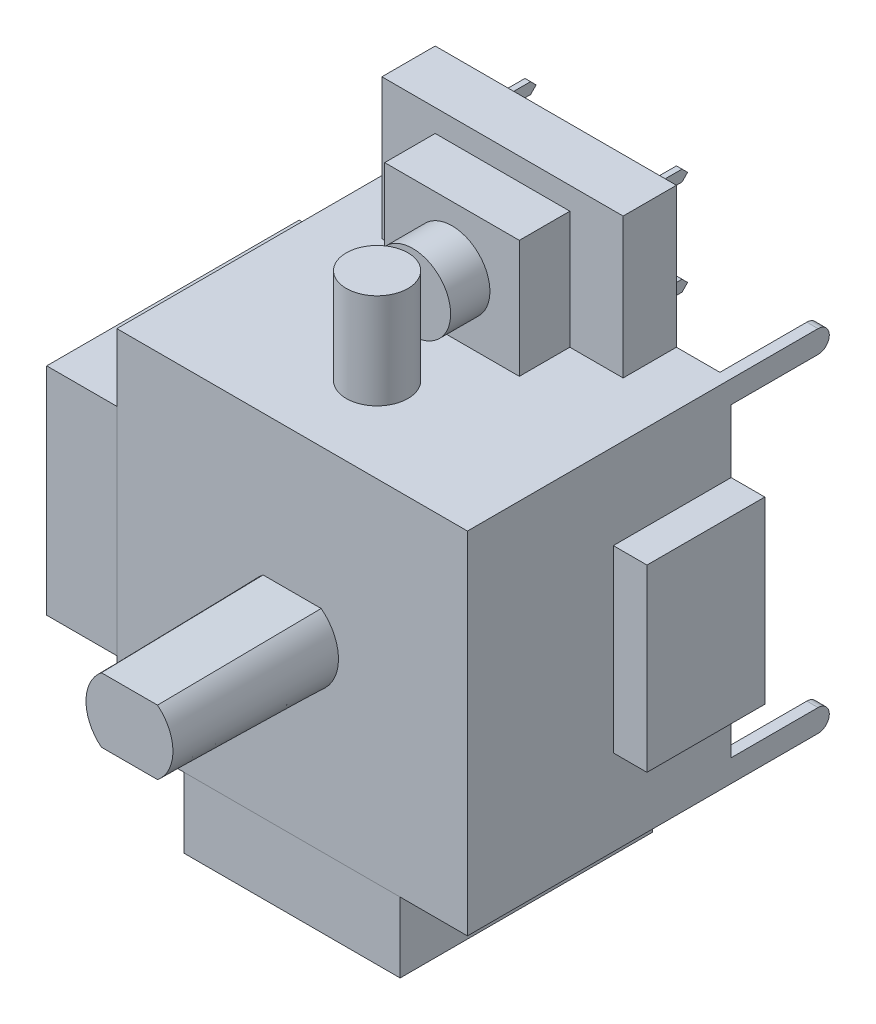
SolidWorks part; units mm, degrees
ref_plane "Front Plane" through (0, 0, 0) normal (0, 0, 1) x (1, 0, 0)
ref_plane "Top Plane" through (0, 0, 0) normal (0, 1, 0) x (1, 0, 0)
ref_plane "Right Plane" through (0, 0, 0) normal (1, 0, 0) x (0, 0, -1)
sketch "Sketch1" plane through (0, 0, 0) normal (0, 0, 1) x (1, 0, 0)
  line L1 (0, 0) -> (15.875, 0)
  line L2 (0, 0) -> (0, 15.875)
  line L3 (0, 15.875) -> (15.875, 15.875)
  line L4 (15.875, 0) -> (15.875, 15.875)
  dimension "D1" = 15.875
extrude "Boss-Extrude1" add sketch "Sketch1" along normal blind 11.938
sketch "Sketch2" plane through (0, 0, 0) normal (0, 0, -1) x (-1, 0, 0)
  line L0 (-7.9375, 15.875) -> (-7.9375, 24.013) construction
  line L1 (-15.875, 15.875) -> (0, 15.875) construction
  line L3 (-13.3985, 15.875) -> (-2.4765, 15.875)
  line L4 (-13.3985, 15.875) -> (-13.3985, 22.225)
  line L5 (-13.3985, 22.225) -> (-2.4765, 22.225)
  line L6 (-2.4765, 15.875) -> (-2.4765, 22.225)
  point P8 (-7.9375, 22.225)
  dimension "D1" = 10.922
  dimension "D2" = 6.35
extrude "Boss-Extrude2" add sketch "Sketch2" against normal blind 2.413
sketch "Sketch3" plane through (15.875, 0, 0) normal (1, 0, 0) x (0, 0, -1)
  line L0 (0, 0) -> (0, 15.875) construction
  line L1 (0, 3.8735) -> (-5.334, 3.8735)
  line L2 (0, 3.8735) -> (0, 12.0015)
  line L3 (0, 12.0015) -> (-5.334, 12.0015)
  line L4 (-5.334, 3.8735) -> (-5.334, 12.0015)
  line L5 (-11.938, 7.9375) -> (0, 7.9375) construction
  line L6 (-11.938, 0) -> (-11.938, 15.875) construction
  point P10 (-5.334, 7.9375)
  dimension "D1" = 8.128
  dimension "D2" = 5.334
extrude "Boss-Extrude3" add sketch "Sketch3" along normal blind 1.524
sketch "Sketch4" plane through (0, 0, 2.413) normal (0, 0, 1) x (1, 0, 0)
  line L0 (7.9375, 22.225) -> (7.9375, 15.875) construction
  line L1 (2.4765, 22.225) -> (13.3985, 22.225) construction
  line L2 (13.3985, 15.875) -> (2.4765, 15.875) construction
  line L3 (15.875, 15.875) -> (0, 15.875) construction
  line L4 (4.8895, 15.875) -> (10.9855, 15.875)
  line L5 (4.8895, 15.875) -> (4.8895, 21.209)
  line L6 (4.8895, 21.209) -> (10.9855, 21.209)
  line L7 (10.9855, 15.875) -> (10.9855, 21.209)
  point P12 (7.9375, 21.209)
  dimension "D1" = 6.096
  dimension "D2" = 5.334
extrude "Boss-Extrude4" add sketch "Sketch4" along normal blind 2.286
sketch "Sketch5" plane through (0, 0, 4.699) normal (0, 0, 1) x (1, 0, 0)
  line L0 (7.9375, 21.209) -> (7.9375, 15.875) construction
  line L1 (10.9855, 21.209) -> (4.8895, 21.209) construction
  line L2 (4.8895, 15.875) -> (10.9855, 15.875) construction
  line L3 (4.8895, 18.542) -> (10.9855, 18.542) construction
  line L4 (4.8895, 21.209) -> (4.8895, 15.875) construction
  line L5 (10.9855, 15.875) -> (10.9855, 21.209) construction
  circle A0 centre (7.9375, 18.542) radius 1.7145
  dimension "D1" = 3.429
extrude "Boss-Extrude5" add sketch "Sketch5" along normal blind 1.778
sketch "Sketch6" plane through (0, 15.875, 0) normal (0, 1, 0) x (1, 0, 0)
  line L0 (7.9375, -11.938) -> (7.9375, -4.699) construction
  line L1 (15.875, -11.938) -> (0, -11.938) construction
  line L2 (10.9855, -4.699) -> (4.8895, -4.699) construction
  circle A0 centre (7.9375, -8.0902) radius 1.397
  dimension "D1" = 2.794
extrude "Boss-Extrude6" add sketch "Sketch6" along normal blind 4.318
sketch "Sketch7" plane through (0, 0, 0) normal (0, -1, 0) x (1, 0, 0)
  line L0 (7.9375, 11.938) -> (7.9375, 0) construction
  line L1 (0, 11.938) -> (15.875, 11.938) construction
  line L2 (0, 0) -> (15.875, 0) construction
  line L4 (3.048, 11.938) -> (12.827, 11.938)
  line L5 (3.048, 11.938) -> (3.048, 0.508)
  line L6 (3.048, 0.508) -> (12.827, 0.508)
  line L7 (12.827, 11.938) -> (12.827, 0.508)
  point P10 (7.9375, 0.508)
  dimension "D1" = 9.779
  dimension "D2" = 11.43
extrude "Boss-Extrude7" add sketch "Sketch7" along normal blind 3.175 separate body
sketch "Sketch8" plane through (0, 0, 0) normal (-1, 0, 0) x (0, 0, 1)
  line L0 (11.938, 7.9375) -> (0, 7.9375) construction
  line L1 (11.938, 15.875) -> (11.938, 0) construction
  line L2 (0, 15.875) -> (0, 0) construction
  line L4 (11.938, 12.827) -> (0.508, 12.827)
  line L5 (11.938, 12.827) -> (11.938, 3.048)
  line L6 (11.938, 3.048) -> (0.508, 3.048)
  line L7 (0.508, 12.827) -> (0.508, 3.048)
  point P10 (0.508, 7.9375)
  dimension "D1" = 9.779
  dimension "D2" = 11.43
extrude "Boss-Extrude8" add sketch "Sketch8" along normal blind 3.175 separate body
sketch "Sketch9" plane through (-3.175, 0, 0) normal (-1, 0, 0) x (0, 0, 1)
  line L0 (11.938, 7.9375) -> (0.508, 7.9375) construction
  line L1 (11.938, 3.048) -> (11.938, 12.827) construction
  line L2 (0.508, 12.827) -> (0.508, 3.048) construction
  line L3 (7.62, 12.4456) -> (7.62, 10.8887)
  line L4 (6.096, 12.4456) -> (6.096, 10.8887)
  line L5 (11.3661, 7.1755) -> (9.8092, 7.1755)
  line L6 (11.3661, 8.6995) -> (9.8092, 8.6995)
  line L7 (6.096, 3.4294) -> (6.096, 4.9863)
  line L8 (7.62, 3.4294) -> (7.62, 4.9863)
  line L10 (2.3499, 7.1755) -> (3.9068, 7.1755)
  line L14 (2.3499, 8.6995) -> (3.9068, 8.6995)
  arc A0 (2.3499, 7.1755) -> (6.096, 3.4294) centre (6.858, 7.9375) ccw
  arc A1 (3.9068, 7.1755) -> (6.096, 4.9863) centre (6.858, 7.9375) ccw
  circle A2 centre (6.858, 7.9375) radius 2.413
  circle A3 centre (6.858, 7.9375) radius 1.8415
  arc A4 (6.096, 12.4456) -> (2.3499, 8.6995) centre (6.858, 7.9375) ccw
  arc A5 (6.096, 10.8887) -> (3.9068, 8.6995) centre (6.858, 7.9375) ccw
  arc A6 (9.8092, 8.6995) -> (7.62, 10.8887) centre (6.858, 7.9375) ccw
  arc A7 (11.3661, 8.6995) -> (7.62, 12.4456) centre (6.858, 7.9375) ccw
  arc A8 (7.62, 4.9863) -> (9.8092, 7.1755) centre (6.858, 7.9375) ccw
  arc A9 (7.62, 3.4294) -> (11.3661, 7.1755) centre (6.858, 7.9375) ccw
  point P25 (6.858, 7.9375)
  dimension "D2" = 9.144
  dimension "D3" = 6.096
  dimension "D4" = 4.826
  dimension "D5" = 3.683
  dimension "D1" = 5.08
  dimension "D8" = 1.524
  dimension "D6" = 4
extrude "Cut-Extrude1" cut sketch "Sketch9" against normal blind 0.508
sketch "Sketch10" plane through (0, -3.175, 0) normal (0, -1, 0) x (1, 0, 0)
  line L0 (7.9375, 11.938) -> (7.9375, 0.508) construction
  line L1 (3.4294, 7.62) -> (4.9863, 7.62)
  line L2 (3.4294, 6.096) -> (4.9863, 6.096)
  line L3 (8.6995, 11.3661) -> (8.6995, 9.8092)
  line L4 (7.1755, 11.3661) -> (7.1755, 9.8092)
  line L5 (12.4456, 6.096) -> (10.8887, 6.096)
  line L6 (12.4456, 7.62) -> (10.8887, 7.62)
  line L7 (8.6995, 2.3499) -> (8.6995, 3.9068)
  line L8 (7.1755, 2.3499) -> (7.1755, 3.9068)
  line L9 (3.048, 11.938) -> (12.827, 11.938) construction
  arc A0 (8.6995, 2.3499) -> (12.4456, 6.096) centre (7.9375, 6.858) ccw
  arc A1 (8.6995, 3.9068) -> (10.8887, 6.096) centre (7.9375, 6.858) ccw
  circle A2 centre (7.9375, 6.858) radius 2.413
  circle A3 centre (7.9375, 6.858) radius 1.8415
  arc A4 (3.4294, 6.096) -> (7.1755, 2.3499) centre (7.9375, 6.858) ccw
  arc A5 (4.9863, 6.096) -> (7.1755, 3.9068) centre (7.9375, 6.858) ccw
  arc A6 (7.1755, 9.8092) -> (4.9863, 7.62) centre (7.9375, 6.858) ccw
  arc A7 (7.1755, 11.3661) -> (3.4294, 7.62) centre (7.9375, 6.858) ccw
  arc A8 (10.8887, 7.62) -> (8.6995, 9.8092) centre (7.9375, 6.858) ccw
  arc A9 (12.4456, 7.62) -> (8.6995, 11.3661) centre (7.9375, 6.858) ccw
  point P18 (7.9375, 6.858)
  dimension "D1" = 4.826
extrude "Cut-Extrude2" cut sketch "Sketch10" against normal blind 0.508
ref_plane "Plane3" through (7.9375, 7.9375, 0) normal (-0.7071, -0.7071, 0) x (-0.7071, 0.7071, 0)
ref_plane "Plane4" through (0, 0, 0) normal (0.7071, -0.7071, 0) x (-0.7071, -0.7071, 0)
ref_axis "Axis2" through (7.9375, 7.9375, -0.5969) along (0, 0, 1)
sketch "Sketch12" plane through (0, 0, 0) normal (0, -1, 0) x (1, 0, 0)
  line L0 (0, 0) -> (0, -4.445)
  line L1 (15.875, 11.938) -> (15.875, 0) construction
  line L2 (0, 0) -> (15.875, 0) construction
  line L3 (15.367, 0) -> (15.367, -4.445)
  dimension "D1" = 4.445
  dimension "D2" = 0.508
extrude "Extrude-Thin1" add sketch "Sketch12" against normal blind 1.016 thin thin type one direction reverse wall 0.508
sketch "Sketch13" plane through (0, 15.875, 0) normal (0, 1, 0) x (1, 0, 0)
  line L0 (0, 0) -> (0, 4.445)
  line L1 (0, 0) -> (0, 4.445) construction
  line L2 (15.367, 0) -> (15.367, 4.445)
  line L3 (15.367, 0) -> (15.367, 4.445) construction
  line L4 (15.367, 0) -> (15.367, 4.445) construction
  point P4 (0, 0)
  point P9 (0, 0)
  point P10 (0, 3.7334)
  point P14 (15.367, 0.3919)
  point P18 (0, 0)
  point P19 (15.367, 0.4434)
extrude "Extrude-Thin2" add sketch "Sketch13" against normal blind 1.016 thin thin type one direction wall 0.508
fillet "Fillet1" radius 0.508 8 edges at (0.254, 1.016, -4.445) (0.254, 15.875, -4.445) (15.621, 15.875, -4.445) (15.621, 1.016, -4.445) (15.621, 0, -4.445) (15.621, 14.859, -4.445) (0.254, 14.859, -4.445) (0.254, 0, -4.445)
ref_plane "Plane5" through (0, -1.5875, 0) normal (0, -1, 0) x (-1, 0, 0)
ref_plane "Plane6" through (-1.5875, 0, 0) normal (-1, 0, 0) x (0, 0, 1)
sketch "Sketch14" plane through (0, -1.5875, 0) normal (0, -1, 0) x (-1, 0, 0)
  line L0 (-7.9375, -0.508) -> (-7.9375, 4.2984) construction
  line L1 (-3.048, -0.508) -> (-12.827, -0.508) construction
  line L2 (-5.3975, -0.508) -> (-5.3975, 4.2984) construction
  line L3 (-10.4775, -0.508) -> (-10.4775, 4.2984) construction
  line L4 (-10.0965, -0.508) -> (-10.0965, 3.6973)
  line L5 (-7.5565, -0.508) -> (-7.5565, 3.6973)
  line L6 (-5.0165, -0.508) -> (-5.0165, 3.6973)
  line L7 (-10.8585, -0.508) -> (-10.8585, 3.6973)
  line L8 (-8.3185, -0.508) -> (-8.3185, 3.6973)
  line L9 (-5.7785, -0.508) -> (-5.7785, 3.6973)
  line L10 (-10.4775, 4.2984) -> (-10.8585, 3.6973)
  line L11 (-7.9375, 4.2984) -> (-8.3185, 3.6973)
  line L12 (-10.0965, 3.6973) -> (-10.4775, 4.2984)
  line L13 (-7.5565, 3.6973) -> (-7.9375, 4.2984)
  line L14 (-5.3975, 4.2984) -> (-5.7785, 3.6973)
  line L15 (-5.0165, 3.6973) -> (-5.3975, 4.2984)
  line L16 (-10.8585, -0.508) -> (-10.8585, 4.2984) construction
  line L17 (-10.0965, -0.508) -> (-10.0965, 4.2984) construction
  line L18 (-8.3185, -0.508) -> (-8.3185, 4.2984) construction
  line L19 (-7.5565, -0.508) -> (-7.5565, 4.2984) construction
  line L20 (-5.7785, -0.508) -> (-5.7785, 4.2984) construction
  line L21 (-5.0165, -0.508) -> (-5.0165, 4.2984) construction
  line L22 (-10.8585, -0.508) -> (-10.0965, -0.508)
  line L23 (-8.3185, -0.508) -> (-7.5565, -0.508)
  line L24 (-5.7785, -0.508) -> (-5.0165, -0.508)
  dimension "D1" = 2.54
  dimension "D2" = 2.54
  dimension "D3" = 0.381
  dimension "D4" = 0.381
extrude "Boss-Extrude9" add sketch "Sketch14" along normal mid plane 0.508
sketch "Sketch15" plane through (-1.5875, 0, 0) normal (-1, 0, 0) x (0, 0, 1)
  line L0 (0.508, 7.9375) -> (-4.2984, 7.9375) construction
  line L1 (0.508, 8.3185) -> (-3.6973, 8.3185)
  line L2 (0.508, 7.5565) -> (-3.6973, 7.5565)
  line L3 (-4.2984, 7.9375) -> (-3.6973, 7.5565)
  line L4 (-3.6973, 8.3185) -> (-4.2984, 7.9375)
  line L5 (0.508, 7.5565) -> (0.508, 8.3185)
  line L6 (0.508, 5.7785) -> (-3.6973, 5.7785)
  line L8 (0.508, 5.0165) -> (-3.6973, 5.0165)
  line L9 (-4.2984, 5.3975) -> (-3.6973, 5.0165)
  line L10 (-3.6973, 5.7785) -> (-4.2984, 5.3975)
  line L11 (0.508, 5.0165) -> (0.508, 5.7785)
  line L12 (0.508, 5.3975) -> (-4.2984, 5.3975) construction
  line L19 (0.508, 10.8585) -> (-3.6973, 10.8585)
  line L20 (0.508, 10.0965) -> (-3.6973, 10.0965)
  line L21 (-4.2984, 10.4775) -> (-3.6973, 10.0965)
  line L22 (-3.6973, 10.8585) -> (-4.2984, 10.4775)
  line L23 (0.508, 10.0965) -> (0.508, 10.8585)
  line L24 (0.508, 10.4775) -> (-4.2984, 10.4775) construction
  line L25 (0.508, 7.9375) -> (-4.2984, 7.9375) construction
  line L26 (0.508, 7.5565) -> (0.508, 8.3185) [skipped]
  line L27 (0.508, 7.5565) -> (-3.6973, 7.5565) [skipped]
  line L28 (-4.2984, 7.9375) -> (-3.6973, 7.5565) [skipped]
  line L29 (-3.6973, 8.3185) -> (-4.2984, 7.9375) [skipped]
  line L30 (0.508, 8.3185) -> (-3.6973, 8.3185) [skipped]
  dimension "D1" = 2
  dimension "D2" = 2
extrude "Boss-Extrude10" add sketch "Sketch15" along normal mid plane 0.508
sketch "Sketch16" plane through (0, 0, 0) normal (0, 0, -1) x (-1, 0, 0)
  line L0 (-13.3985, 22.225) -> (-13.3985, 15.875) construction
  line L1 (-11.3665, 20.701) -> (-11.1125, 20.701)
  line L2 (-11.3665, 20.701) -> (-11.3665, 20.193)
  line L3 (-11.3665, 20.193) -> (-11.1125, 20.193)
  line L4 (-11.1125, 20.701) -> (-11.1125, 20.193)
  line L5 (-2.4765, 22.225) -> (-13.3985, 22.225) construction
  line L6 (-4.5085, 20.701) -> (-4.2545, 20.701)
  line L7 (-4.5085, 20.701) -> (-4.5085, 20.193)
  line L8 (-4.5085, 20.193) -> (-4.2545, 20.193)
  line L9 (-4.2545, 20.701) -> (-4.2545, 20.193)
  line L10 (-4.5085, 16.383) -> (-4.2545, 16.383)
  line L11 (-4.5085, 16.383) -> (-4.5085, 15.875)
  line L12 (-4.5085, 15.875) -> (-4.2545, 15.875)
  line L13 (-4.2545, 16.383) -> (-4.2545, 15.875)
  line L14 (-11.3665, 16.383) -> (-11.1125, 16.383)
  line L15 (-11.3665, 16.383) -> (-11.3665, 15.875)
  line L16 (-11.3665, 15.875) -> (-11.1125, 15.875)
  line L17 (-11.1125, 16.383) -> (-11.1125, 15.875)
  dimension "D1" = 2.032
  dimension "D2" = 1.524
  dimension "D3" = 0.254
  dimension "D4" = 0.508
  dimension "D5" = 2
  dimension "D6" = 2
extrude "Boss-Extrude11" add sketch "Sketch16" along normal blind 2.54
chamfer "Chamfer1" distance 0.254 angle 45 8 edges at (11.2395, 15.875, -2.54) (11.2395, 16.383, -2.54) (4.3815, 15.875, -2.54) (4.3815, 16.383, -2.54) (4.3815, 20.193, -2.54) (4.3815, 20.701, -2.54) (11.2395, 20.193, -2.54) (11.2395, 20.701, -2.54)
sketch "Sketch17" plane through (0, 0, 11.938) normal (0, 0, 1) x (1, 0, 0)
  line L0 (6.6675, 9.398) -> (9.2075, 9.398)
  line L1 (6.6675, 6.477) -> (9.2075, 6.477)
  line L2 (15.875, 0) -> (15.875, 15.875) construction
  line L3 (15.875, 15.875) -> (0, 15.875) construction
  arc A0 (6.6675, 9.398) -> (6.6675, 6.477) centre (7.8451, 7.9375) ccw
  arc A1 (9.2075, 9.398) -> (9.2075, 6.477) centre (8.0299, 7.9375) cw
  point P8 (15.875, 7.9375)
  point P9 (7.9375, 9.398)
  point P12 (7.9375, 15.875)
  point P13 (6.6889, 9.398)
  point P14 (9.6223, 9.398)
  point P15 (5.969, 7.9375)
  dimension "D2" = 3.937
  dimension "D3" = 2.54
  dimension "D1" = 2.921
extrude "Boss-Extrude12" add sketch "Sketch17" along normal blind 7.366
draft "Draft1" type of draft neutral plane draft angle 1 faces to draft 4 face at (9.5568, 7.9375, 15.621) face at (7.9375, 9.398, 15.621) face at (6.3182, 7.9375, 15.621) face at (7.9375, 6.477, 15.621) neutral plane through (7.8451, 7.9375, 19.304) neutral plane normal (0, 0, 1) parameters "D1"=1
